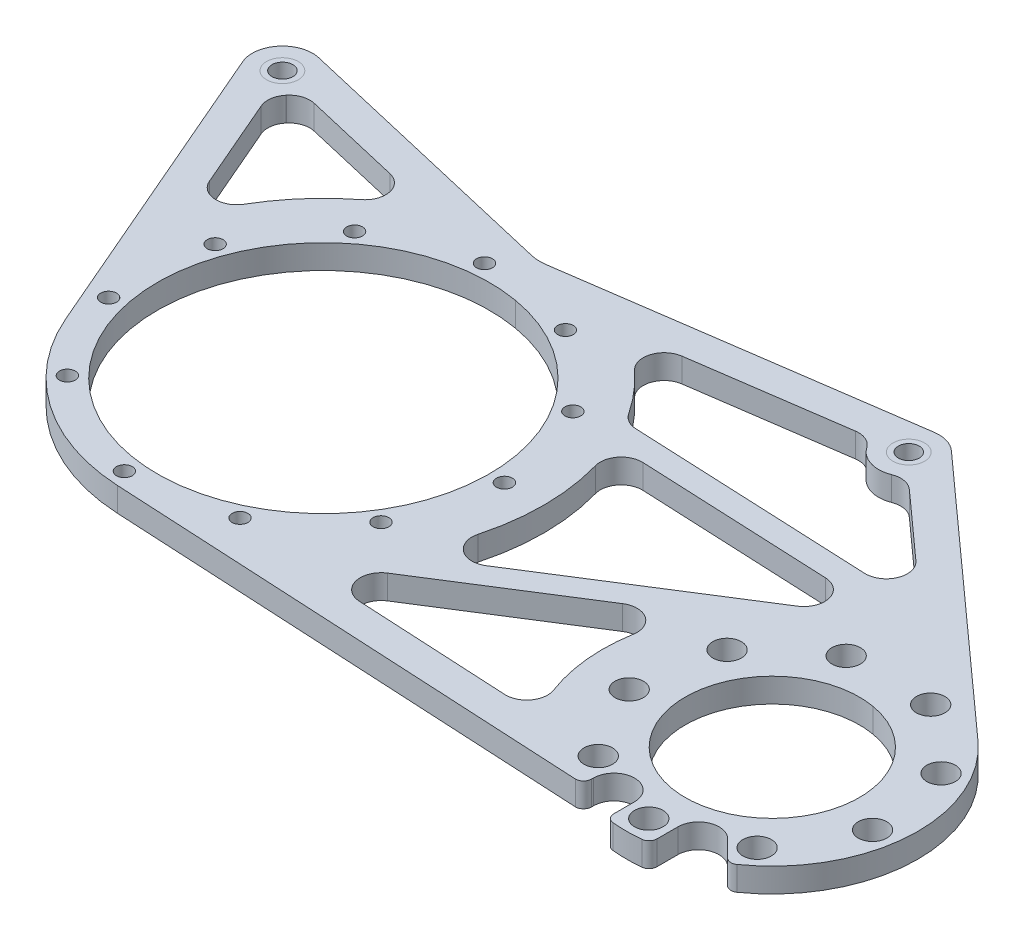
SolidWorks part; units mm, degrees
material "6061-T6 (SS)"
ref_plane "X-Y Datum" through (0, 0, 0) normal (0, 0, 1) x (1, 0, 0)
ref_plane "X-Z Datum" through (0, 0, 0) normal (0, 1, 0) x (1, 0, 0)
ref_plane "Y-Z Datum" through (0, 0, 0) normal (1, 0, 0) x (0, 0, -1)
sketch "Sketch2" plane through (0, 31.3819, 0) normal (0, 1, 0) x (1, 0, 0)
  line L0 (-693.7583, -176.702) -> (-693.7583, -183.2747) construction
  line L1 (-680.0808, -183.2747) -> (-680.0808, -176.702) construction
  line L2 (-668.9846, -172.1058) -> (-663.7197, -177.3707) construction
  line L3 (-693.7583, -176.702) -> (-693.7583, -183.2747)
  line L4 (-680.0808, -183.2747) -> (-680.0808, -176.702)
  line L5 (-668.9846, -172.1058) -> (-663.7197, -177.3707)
  line L6 (-966.641, -0.354) -> (-738.041, -0.354)
  line L7 (-727.7656, -5.5904) -> (-649.7224, -113.0358)
  line L9 (-977.8288, -19.0644) -> (-913.2312, -139.3061)
  line L10 (-706.7583, -177.279) -> (-706.7583, -176.702) construction
  line L11 (-706.7583, -177.279) -> (-706.7583, -176.702)
  line L12 (-861.9259, -171.8334) -> (-709.2983, -179.819)
  line L13 (-858.691, -110.0055) -> (-686.9195, -140.054) construction
  line L14 (-972.26, -24.9963) -> (-955.4664, -39.59) construction
  line L15 (-941.4162, -26.937) -> (-954.1775, -8.712) construction
  line L16 (-751.1929, -14.159) -> (-755.4346, -35.9995) construction
  line L17 (-737.4517, -41.8408) -> (-728.049, -21.6768) construction
  line L18 (-972.26, -24.9963) -> (-955.4664, -39.59)
  line L19 (-941.4162, -26.937) -> (-954.1775, -8.712)
  line L20 (-751.1929, -14.159) -> (-755.4346, -35.9995)
  line L21 (-737.4517, -41.8408) -> (-728.049, -21.6768)
  line L22 (-949.2186, -22.8753) -> (-746.0843, -28.2904)
  line L23 (-739.7146, -30.7335) -> (-656.1751, -105.8723)
  line L24 (-957.9647, -36.1729) -> (-915.5404, -134.527)
  arc A0 (-710.607, -179.4559) -> (-706.7583, -177.279) centre (-709.2983, -177.279) ccw construction
  arc A1 (-693.7583, -176.702) -> (-706.7583, -176.702) centre (-700.2583, -176.702) ccw construction
  arc A2 (-693.7583, -183.2747) -> (-691.4697, -185.8023) centre (-691.2183, -183.2747) ccw construction
  arc A3 (-691.4697, -185.8023) -> (-682.3694, -185.8023) centre (-686.9195, -140.054) ccw construction
  arc A4 (-682.3694, -185.8023) -> (-680.0808, -183.2747) centre (-682.6208, -183.2747) ccw construction
  arc A5 (-668.9846, -172.1058) -> (-680.0808, -176.702) centre (-673.5808, -176.702) ccw construction
  arc A6 (-663.7197, -177.3707) -> (-660.4619, -177.6519) centre (-661.9236, -175.5746) ccw construction
  arc A7 (-660.4619, -177.6519) -> (-710.607, -179.4559) centre (-686.9195, -140.054) ccw construction
  circle A8 centre (-858.691, -110.0055) radius 52.3875 construction
  circle A9 centre (-858.691, -110.0055) radius 61.9125 construction
  circle A10 centre (-738.041, -13.054) radius 12.7 construction
  circle A11 centre (-966.641, -13.054) radius 12.7 construction
  arc A12 (-710.607, -179.4559) -> (-706.7583, -177.279) centre (-709.2983, -177.279) ccw
  arc A13 (-693.7583, -176.702) -> (-706.7583, -176.702) centre (-700.2583, -176.702) ccw
  arc A14 (-693.7583, -183.2747) -> (-691.4697, -185.8023) centre (-691.2183, -183.2747) ccw
  arc A15 (-691.4697, -185.8023) -> (-682.3694, -185.8023) centre (-686.9195, -140.054) ccw
  arc A16 (-682.3694, -185.8023) -> (-680.0808, -183.2747) centre (-682.6208, -183.2747) ccw
  arc A17 (-668.9846, -172.1058) -> (-680.0808, -176.702) centre (-673.5808, -176.702) ccw
  arc A18 (-663.7197, -177.3707) -> (-660.4619, -177.6519) centre (-661.9236, -175.5746) ccw
  arc A19 (-660.4619, -177.6519) -> (-710.607, -179.4559) centre (-686.9195, -140.054) ccw
  circle A20 centre (-858.691, -110.0055) radius 52.3875
  circle A21 centre (-858.691, -110.0055) radius 61.9125
  circle A22 centre (-738.041, -13.054) radius 12.7
  circle A23 centre (-966.641, -13.054) radius 12.7
  circle A31 centre (-864.6648, -166.8424) radius 2.5 construction
  circle A39 centre (-864.6648, -166.8424) radius 2.5
  circle A40 centre (-686.9195, -140.054) radius 27.4955 construction
  circle A41 centre (-686.9195, -140.054) radius 27.4955
  circle A42 centre (-711.9883, -169.9297) radius 4.5 construction
  circle A43 centre (-725.3271, -146.8263) radius 4.5 construction
  circle A44 centre (-720.6945, -120.554) radius 4.5 construction
  circle A45 centre (-700.2583, -103.406) radius 4.5 construction
  circle A46 centre (-673.5808, -103.406) radius 4.5 construction
  circle A47 centre (-653.1446, -120.554) radius 4.5 construction
  circle A48 centre (-648.512, -146.8263) radius 4.5 construction
  circle A49 centre (-661.8508, -169.9297) radius 4.5 construction
  circle A50 centre (-686.9195, -179.054) radius 4.5 construction
  circle A51 centre (-711.9883, -169.9297) radius 4.5
  circle A52 centre (-725.3271, -146.8263) radius 4.5
  circle A53 centre (-720.6945, -120.554) radius 4.5
  circle A54 centre (-700.2583, -103.406) radius 4.5
  circle A55 centre (-673.5808, -103.406) radius 4.5
  circle A56 centre (-653.1446, -120.554) radius 4.5
  circle A57 centre (-648.512, -146.8263) radius 4.5
  circle A58 centre (-661.8508, -169.9297) radius 4.5
  circle A59 centre (-686.9195, -179.054) radius 4.5
  circle A60 centre (-966.641, -13.054) radius 3.3
  circle A61 centre (-738.041, -13.054) radius 3.3
  arc A62 (-955.4664, -39.59) -> (-941.4162, -26.937) centre (-949.2186, -32.4003) ccw construction
  arc A63 (-749.3237, -37.1863) -> (-742.8448, -38.4445) centre (-746.0843, -37.8154) ccw construction
  arc A64 (-742.8448, -38.4445) -> (-749.3237, -37.1863) centre (-746.0843, -37.8154) ccw construction
  arc A65 (-755.4346, -35.9995) -> (-737.4517, -41.8408) centre (-746.0843, -37.8154) ccw construction
  arc A66 (-955.4664, -39.59) -> (-941.4162, -26.937) centre (-949.2186, -32.4003) ccw
  arc A67 (-749.3237, -37.1863) -> (-742.8448, -38.4445) centre (-746.0843, -37.8154) ccw
  arc A68 (-742.8448, -38.4445) -> (-749.3237, -37.1863) centre (-746.0843, -37.8154) ccw
  arc A69 (-755.4346, -35.9995) -> (-737.4517, -41.8408) centre (-746.0843, -37.8154) ccw
  circle A70 centre (-949.2186, -32.4003) radius 3.3
  circle A71 centre (-949.2186, -32.4003) radius 9.525
  circle A72 centre (-746.0843, -37.8154) radius 9.525
  point P94 (-949.2186, -32.4003)
  dimension "D1" = 6.6
  dimension "D2" = 6.6
  dimension "D3" = 6.6
extrude "Boss-Extrude1" add sketch "Sketch2" along normal blind 7.62 contours A21 A39 A20 | A18 A19 A12 L11 A13 L3 A14 A15 A16 L4 A17 L5 A59 A58 A57 A56 A55 A54 A53 A52 A51 A41 | L13 A21 L12 A12 A19 | A21 L13 A19 L23 L21 A69 L20 L22 L19 A66 L18 L24 | A69 A72 A68 A67 | A72 L22 L20 | A72 L21 L23 | A71 L24 L18 | A71 L19 L22 | A71 A66 L22 A70 region at (-700.2583, 31.3819, 168.9016) region at (-773.051, 31.3819, 154.3682) region at (-890.9045, 31.3819, 160.8157) region at (-806.8861, 31.3819, 67.2042) region at (-956.9478, 31.3819, 38.0512) region at (-736.2382, 31.3819, 35.8095) region at (-956.6903, 31.3819, 37.8629) region at (-748.9437, 31.3819, 46.6182) region at (-752.4763, 31.3819, 29.8585) region at (-944.5842, 31.3819, 23.8004)
sketch "Sketch3" plane through (0, 31.3819, 0) normal (0, -1, 0) x (1, 0, 0)
  line L1 (-949.2186, 22.8753) -> (-746.0843, 28.2904) construction
  line L5 (-861.9259, 171.8334) -> (-709.2983, 179.819) construction
  line L6 (-977.8288, 19.0644) -> (-913.2312, 139.3061) construction
  line L7 (-727.7656, 5.5904) -> (-649.7224, 113.0358) construction
  line L13 (-751.1929, 14.159) -> (-755.4346, 35.9995) construction
  line L16 (-966.641, 0.354) -> (-738.041, 0.354) construction
  line L19 (-663.7197, 177.3707) -> (-668.9846, 172.1058)
  line L20 (-680.0808, 176.702) -> (-680.0808, 183.2747)
  line L21 (-693.7583, 183.2747) -> (-693.7583, 176.702)
  line L22 (-706.7583, 176.702) -> (-706.7583, 177.279)
  line L23 (-663.7197, 177.3707) -> (-668.9846, 172.1058)
  line L24 (-680.0808, 176.702) -> (-680.0808, 183.2747)
  line L25 (-693.7583, 183.2747) -> (-693.7583, 176.702)
  line L26 (-706.7583, 176.702) -> (-706.7583, 177.279)
  line L28 (-861.9259, 171.8334) -> (-709.2983, 179.819)
  line L29 (-977.8288, 19.0644) -> (-913.2312, 139.3061)
  line L30 (-727.7656, 5.5904) -> (-649.7224, 113.0358)
  line L31 (-966.641, 0.354) -> (-738.041, 0.354)
  line L34 (-737.4517, 41.8408) -> (-728.049, 21.6768) construction
  line L35 (-972.26, 24.9963) -> (-955.4664, 39.59) construction
  line L36 (-947.0539, 23.1246) -> (-856.9722, 44.1471)
  line L37 (-856.9722, 44.1471) -> (-747.4408, 28.3875)
  line L44 (-941.4162, 26.937) -> (-954.1775, 8.712) construction
  line L45 (-957.9647, 36.1729) -> (-915.5404, 134.527) construction
  line L46 (-739.7146, 30.7335) -> (-656.1751, 105.8723) construction
  line L47 (-861.9259, 171.8334) -> (-709.2983, 179.819)
  line L48 (-977.8288, 19.0644) -> (-913.2312, 139.3061)
  line L49 (-727.7656, 5.5904) -> (-649.7224, 113.0358)
  line L50 (-966.641, 0.354) -> (-738.041, 0.354)
  line L51 (-949.2186, 22.8753) -> (-746.0843, 28.2904)
  line L52 (-751.1929, 14.159) -> (-755.4346, 35.9995)
  line L53 (-737.4517, 41.8408) -> (-728.049, 21.6768)
  line L54 (-972.26, 24.9963) -> (-955.4664, 39.59)
  line L55 (-941.4162, 26.937) -> (-954.1775, 8.712)
  line L56 (-957.9647, 36.1729) -> (-915.5404, 134.527)
  line L57 (-739.7146, 30.7335) -> (-656.1751, 105.8723)
  arc A1 (-737.4517, 41.8408) -> (-755.4346, 35.9995) centre (-746.0843, 37.8154) ccw construction
  circle A3 centre (-966.641, 13.054) radius 12.7
  circle A5 centre (-966.641, 13.054) radius 12.7
  circle A7 centre (-738.041, 13.054) radius 12.7
  circle A9 centre (-738.041, 13.054) radius 12.7
  circle A11 centre (-858.691, 110.0055) radius 61.9125
  circle A13 centre (-858.691, 110.0055) radius 61.9125
  circle A15 centre (-858.691, 110.0055) radius 52.3875
  circle A17 centre (-858.691, 110.0055) radius 52.3875
  circle A19 centre (-686.9195, 140.054) radius 27.4955
  circle A21 centre (-686.9195, 140.054) radius 27.4955
  circle A23 centre (-864.6648, 166.8424) radius 2.5
  circle A25 centre (-864.6648, 166.8424) radius 2.5
  circle A51 centre (-720.6945, 120.554) radius 4.5
  circle A52 centre (-720.6945, 120.554) radius 4.5
  circle A68 centre (-725.3271, 146.8263) radius 4.5
  circle A69 centre (-725.3271, 146.8263) radius 4.5
  circle A70 centre (-711.9883, 169.9297) radius 4.5
  circle A71 centre (-711.9883, 169.9297) radius 4.5
  circle A72 centre (-738.041, 13.054) radius 3.3
  circle A73 centre (-738.041, 13.054) radius 3.3
  circle A74 centre (-966.641, 13.054) radius 3.3
  circle A75 centre (-966.641, 13.054) radius 3.3
  circle A76 centre (-686.9195, 179.054) radius 4.5
  circle A77 centre (-686.9195, 179.054) radius 4.5
  circle A78 centre (-661.8508, 169.9297) radius 4.5
  circle A79 centre (-661.8508, 169.9297) radius 4.5
  circle A80 centre (-648.512, 146.8263) radius 4.5
  circle A81 centre (-648.512, 146.8263) radius 4.5
  circle A82 centre (-653.1446, 120.554) radius 4.5
  circle A83 centre (-653.1446, 120.554) radius 4.5
  circle A84 centre (-673.5808, 103.406) radius 4.5
  circle A85 centre (-673.5808, 103.406) radius 4.5
  circle A86 centre (-700.2583, 103.406) radius 4.5
  circle A87 centre (-700.2583, 103.406) radius 4.5
  arc A95 (-710.607, 179.4559) -> (-660.4619, 177.6519) centre (-686.9195, 140.054) ccw
  arc A96 (-660.4619, 177.6519) -> (-663.7197, 177.3707) centre (-661.9236, 175.5746) ccw
  arc A97 (-680.0808, 176.702) -> (-668.9846, 172.1058) centre (-673.5808, 176.702) ccw
  arc A98 (-680.0808, 183.2747) -> (-682.3694, 185.8023) centre (-682.6208, 183.2747) ccw
  arc A99 (-682.3694, 185.8023) -> (-691.4697, 185.8023) centre (-686.9195, 140.054) ccw
  arc A100 (-691.4697, 185.8023) -> (-693.7583, 183.2747) centre (-691.2183, 183.2747) ccw
  arc A101 (-706.7583, 176.702) -> (-693.7583, 176.702) centre (-700.2583, 176.702) ccw
  arc A102 (-706.7583, 177.279) -> (-710.607, 179.4559) centre (-709.2983, 177.279) ccw
  arc A103 (-710.607, 179.4559) -> (-660.4619, 177.6519) centre (-686.9195, 140.054) ccw
  arc A104 (-660.4619, 177.6519) -> (-663.7197, 177.3707) centre (-661.9236, 175.5746) ccw
  arc A105 (-680.0808, 176.702) -> (-668.9846, 172.1058) centre (-673.5808, 176.702) ccw
  arc A106 (-680.0808, 183.2747) -> (-682.3694, 185.8023) centre (-682.6208, 183.2747) ccw
  arc A107 (-682.3694, 185.8023) -> (-691.4697, 185.8023) centre (-686.9195, 140.054) ccw
  arc A108 (-691.4697, 185.8023) -> (-693.7583, 183.2747) centre (-691.2183, 183.2747) ccw
  arc A109 (-706.7583, 176.702) -> (-693.7583, 176.702) centre (-700.2583, 176.702) ccw
  arc A110 (-706.7583, 177.279) -> (-710.607, 179.4559) centre (-709.2983, 177.279) ccw
  circle A152 centre (-746.0843, 37.8154) radius 9.525
  circle A153 centre (-746.0843, 37.8154) radius 9.525
  circle A154 centre (-949.2186, 32.4003) radius 9.525
  circle A155 centre (-949.2186, 32.4003) radius 9.525
  circle A156 centre (-949.2186, 32.4003) radius 3.3
  circle A157 centre (-949.2186, 32.4003) radius 3.3
  arc A158 (-941.4162, 26.937) -> (-955.4664, 39.59) centre (-949.2186, 32.4003) ccw construction
  arc A159 (-742.8448, 38.4445) -> (-749.3237, 37.1863) centre (-746.0843, 37.8154) ccw
  arc A160 (-749.3237, 37.1863) -> (-742.8448, 38.4445) centre (-746.0843, 37.8154) ccw
  arc A161 (-742.8448, 38.4445) -> (-749.3237, 37.1863) centre (-746.0843, 37.8154) ccw
  arc A162 (-749.3237, 37.1863) -> (-742.8448, 38.4445) centre (-746.0843, 37.8154) ccw
  arc A163 (-737.4517, 41.8408) -> (-755.4346, 35.9995) centre (-746.0843, 37.8154) ccw
  arc A164 (-941.4162, 26.937) -> (-955.4664, 39.59) centre (-949.2186, 32.4003) ccw
  dimension "D24" = 0
  dimension "D25" = 0
  dimension "D26" = 90.0818
  dimension "D27" = 21.0225
  dimension "D1" = 0
  dimension "D2" = 0
  dimension "D3" = 0
  dimension "D4" = 0
  dimension "D5" = 0
  dimension "D6" = 0
  dimension "D14" = 0
  dimension "D15" = 0
  dimension "D16" = 0
  dimension "D17" = 0
  dimension "D18" = 0
  dimension "D19" = 0
  dimension "D20" = 0
  dimension "D21" = 0
  dimension "D22" = 0
  dimension "D23" = 0
  dimension "D52" = 0
  dimension "D53" = 0
  dimension "D54" = 0
  dimension "D55" = 0
ref_point "Point1"
ref_point "Point2"
ref_plane "Plane1" through (-858.691, 31.3819, 110.0055) normal (0.985, 0, 0.1723) x (0.1723, 0, -0.985)
ref_plane "Plane2" through (-686.9195, 31.3819, 140.054) normal (-0.985, 0, -0.1723) x (-0.1723, 0, 0.985)
split line "Split Line1"
split line "Split Line2"
ref_axis "Axis1" through (-858.691, 39.0019, 110.0055) along (0, -1, 0)
ref_axis "Axis2" through (-686.9195, 39.0019, 140.054) along (0, -1, 0)
extrude "Cut-Extrude1" cut sketch "Sketch3" against normal through all contours L36 L55 L51 L52 L37 | A155 L51 L55 L36 | A153 L37 L52 L51 region at (-751.5495, 31.3819, 28.5688) region at (-850.6911, 31.3819, 31.7926) region at (-945.2616, 31.3819, 23.2848)
fillet "Fillet2" radius 12.7 1 edges at (-856.9722, 35.1919, 44.1471)
sketch "Sketch4" plane through (0, 31.3819, 0) normal (0, -1, 0) x (1, 0, 0)
  line L0 (-861.9259, 171.8334) -> (-709.2983, 179.819) construction
  line L1 (-727.7656, 5.5904) -> (-649.7224, 113.0358) construction
  line L2 (-977.8288, 19.0644) -> (-913.2312, 139.3061) construction
  line L4 (-706.7583, 176.702) -> (-706.7583, 177.279)
  line L5 (-663.7197, 177.3707) -> (-668.9846, 172.1058)
  line L6 (-680.0808, 176.702) -> (-680.0808, 183.2747)
  line L7 (-693.7583, 183.2747) -> (-693.7583, 176.702)
  line L8 (-706.7583, 176.702) -> (-706.7583, 177.279)
  line L9 (-663.7197, 177.3707) -> (-668.9846, 172.1058)
  line L10 (-680.0808, 176.702) -> (-680.0808, 183.2747)
  line L11 (-693.7583, 183.2747) -> (-693.7583, 176.702)
  line L13 (-966.641, 0.354) -> (-738.041, 0.354) construction
  line L14 (-861.9259, 171.8334) -> (-709.2983, 179.819)
  line L15 (-727.7656, 5.5904) -> (-649.7224, 113.0358)
  line L16 (-977.8288, 19.0644) -> (-913.2312, 139.3061)
  line L17 (-861.9259, 171.8334) -> (-709.2983, 179.819) construction
  line L19 (-966.641, 0.354) -> (-738.041, 0.354)
  line L20 (-924.6037, 87.863) -> (-948.1369, 33.3048)
  line L21 (-948.1369, 33.3048) -> (-888.5504, 47.2106)
  line L22 (-732.3805, 168.4374) -> (-812.7818, 164.2308)
  line L23 (-812.7818, 164.2308) -> (-733.9678, 114.3873)
  line L24 (-799.833, 147.0258) -> (-703.8013, 86.2934)
  line L25 (-703.8013, 86.2934) -> (-794.9695, 82.1785)
  line L26 (-824.108, 49.6832) -> (-755.4008, 39.7974)
  line L27 (-798.9847, 74.3695) -> (-701.5009, 78.7695)
  line L28 (-701.5009, 78.7695) -> (-739.4428, 44.643)
  line L29 (-977.8288, 19.0644) -> (-913.2312, 139.3061) construction
  line L30 (-727.7656, 5.5904) -> (-649.7224, 113.0358) construction
  line L31 (-966.641, 0.354) -> (-738.041, 0.354) construction
  line L32 (-663.7197, 177.3707) -> (-668.9846, 172.1058)
  line L33 (-680.0808, 176.702) -> (-680.0808, 183.2747)
  line L34 (-693.7583, 183.2747) -> (-693.7583, 176.702)
  line L35 (-706.7583, 176.702) -> (-706.7583, 177.279)
  line L36 (-663.7197, 177.3707) -> (-668.9846, 172.1058)
  line L37 (-680.0808, 176.702) -> (-680.0808, 183.2747)
  line L38 (-693.7583, 183.2747) -> (-693.7583, 176.702)
  line L39 (-706.7583, 176.702) -> (-706.7583, 177.279)
  line L40 (-949.2186, 22.8753) -> (-746.0843, 28.2904) construction
  line L41 (-751.1929, 14.159) -> (-755.4346, 35.9995) construction
  line L42 (-737.4517, 41.8408) -> (-728.049, 21.6768) construction
  line L43 (-972.26, 24.9963) -> (-955.4664, 39.59) construction
  line L44 (-941.4162, 26.937) -> (-954.1775, 8.712) construction
  line L45 (-957.9647, 36.1729) -> (-915.5404, 134.527) construction
  line L46 (-739.7146, 30.7335) -> (-656.1751, 105.8723) construction
  line L47 (-861.9259, 171.8334) -> (-709.2983, 179.819)
  line L48 (-977.8288, 19.0644) -> (-913.2312, 139.3061)
  line L49 (-727.7656, 5.5904) -> (-649.7224, 113.0358)
  line L50 (-966.641, 0.354) -> (-738.041, 0.354)
  line L51 (-949.2186, 22.8753) -> (-746.0843, 28.2904)
  line L52 (-751.1929, 14.159) -> (-755.4346, 35.9995)
  line L53 (-737.4517, 41.8408) -> (-728.049, 21.6768)
  line L54 (-972.26, 24.9963) -> (-955.4664, 39.59)
  line L55 (-941.4162, 26.937) -> (-954.1775, 8.712)
  line L56 (-957.9647, 36.1729) -> (-915.5404, 134.527)
  line L57 (-739.7146, 30.7335) -> (-656.1751, 105.8723)
  line L58 (-947.0539, 23.1246) -> (-859.3005, 43.6037) construction
  line L60 (-854.6056, 43.8066) -> (-747.4408, 28.3875) construction
  circle A1 centre (-858.691, 110.0055) radius 52.3875
  circle A2 centre (-858.691, 110.0055) radius 52.3875
  circle A3 centre (-858.691, 110.0055) radius 61.9125
  circle A4 centre (-858.691, 110.0055) radius 61.9125
  circle A5 centre (-738.041, 13.054) radius 12.7
  circle A6 centre (-738.041, 13.054) radius 12.7
  circle A7 centre (-966.641, 13.054) radius 12.7
  circle A8 centre (-966.641, 13.054) radius 12.7
  circle A17 centre (-864.6648, 166.8424) radius 2.5
  circle A18 centre (-864.6648, 166.8424) radius 2.5
  circle A19 centre (-686.9195, 140.054) radius 27.4955
  circle A20 centre (-686.9195, 140.054) radius 27.4955
  circle A21 centre (-725.3271, 146.8263) radius 4.5
  circle A22 centre (-725.3271, 146.8263) radius 4.5
  circle A23 centre (-720.6945, 120.554) radius 4.5
  circle A24 centre (-720.6945, 120.554) radius 4.5
  circle A31 centre (-661.8508, 169.9297) radius 4.5
  circle A32 centre (-661.8508, 169.9297) radius 4.5
  circle A33 centre (-686.9195, 179.054) radius 4.5
  circle A34 centre (-686.9195, 179.054) radius 4.5
  circle A35 centre (-966.641, 13.054) radius 3.3
  circle A36 centre (-966.641, 13.054) radius 3.3
  circle A37 centre (-738.041, 13.054) radius 3.3
  circle A38 centre (-738.041, 13.054) radius 3.3
  circle A39 centre (-711.9883, 169.9297) radius 4.5
  circle A40 centre (-711.9883, 169.9297) radius 4.5
  circle A41 centre (-700.2583, 103.406) radius 4.5
  circle A42 centre (-700.2583, 103.406) radius 4.5
  circle A43 centre (-673.5808, 103.406) radius 4.5
  circle A44 centre (-673.5808, 103.406) radius 4.5
  circle A45 centre (-653.1446, 120.554) radius 4.5
  circle A46 centre (-653.1446, 120.554) radius 4.5
  circle A47 centre (-648.512, 146.8263) radius 4.5
  circle A48 centre (-648.512, 146.8263) radius 4.5
  arc A49 (-888.5504, 47.2106) -> (-924.6037, 87.863) centre (-858.691, 110.0055) cw
  arc A50 (-732.3805, 168.4374) -> (-733.9678, 114.3873) centre (-686.9195, 140.054) ccw
  arc A51 (-799.833, 147.0258) -> (-794.9695, 82.1785) centre (-858.691, 110.0055) cw
  arc A52 (-824.108, 49.6832) -> (-798.9847, 74.3695) centre (-858.691, 110.0055) ccw
  arc A53 (-737.4517, 41.8408) -> (-755.4346, 35.9995) centre (-746.0843, 37.8154) ccw construction
  circle A54 centre (-966.641, 13.054) radius 12.7
  circle A55 centre (-966.641, 13.054) radius 12.7
  arc A56 (-706.7583, 177.279) -> (-710.607, 179.4559) centre (-709.2983, 177.279) ccw
  arc A57 (-710.607, 179.4559) -> (-660.4619, 177.6519) centre (-686.9195, 140.054) ccw
  arc A58 (-660.4619, 177.6519) -> (-663.7197, 177.3707) centre (-661.9236, 175.5746) ccw
  arc A59 (-680.0808, 176.702) -> (-668.9846, 172.1058) centre (-673.5808, 176.702) ccw
  arc A60 (-680.0808, 183.2747) -> (-682.3694, 185.8023) centre (-682.6208, 183.2747) ccw
  arc A61 (-682.3694, 185.8023) -> (-691.4697, 185.8023) centre (-686.9195, 140.054) ccw
  arc A62 (-691.4697, 185.8023) -> (-693.7583, 183.2747) centre (-691.2183, 183.2747) ccw
  arc A63 (-706.7583, 176.702) -> (-693.7583, 176.702) centre (-700.2583, 176.702) ccw
  arc A64 (-706.7583, 177.279) -> (-710.607, 179.4559) centre (-709.2983, 177.279) ccw
  arc A65 (-710.607, 179.4559) -> (-660.4619, 177.6519) centre (-686.9195, 140.054) ccw
  arc A66 (-660.4619, 177.6519) -> (-663.7197, 177.3707) centre (-661.9236, 175.5746) ccw
  arc A67 (-680.0808, 176.702) -> (-668.9846, 172.1058) centre (-673.5808, 176.702) ccw
  arc A68 (-680.0808, 183.2747) -> (-682.3694, 185.8023) centre (-682.6208, 183.2747) ccw
  arc A69 (-682.3694, 185.8023) -> (-691.4697, 185.8023) centre (-686.9195, 140.054) ccw
  arc A70 (-691.4697, 185.8023) -> (-693.7583, 183.2747) centre (-691.2183, 183.2747) ccw
  arc A71 (-706.7583, 176.702) -> (-693.7583, 176.702) centre (-700.2583, 176.702) ccw
  circle A72 centre (-738.041, 13.054) radius 12.7
  circle A73 centre (-738.041, 13.054) radius 12.7
  circle A74 centre (-858.691, 110.0055) radius 61.9125
  circle A75 centre (-858.691, 110.0055) radius 61.9125
  circle A76 centre (-858.691, 110.0055) radius 52.3875
  circle A77 centre (-858.691, 110.0055) radius 52.3875
  circle A78 centre (-686.9195, 140.054) radius 27.4955
  circle A79 centre (-686.9195, 140.054) radius 27.4955
  circle A80 centre (-864.6648, 166.8424) radius 2.5
  circle A81 centre (-864.6648, 166.8424) radius 2.5
  circle A96 centre (-720.6945, 120.554) radius 4.5
  circle A97 centre (-720.6945, 120.554) radius 4.5
  circle A98 centre (-725.3271, 146.8263) radius 4.5
  circle A99 centre (-725.3271, 146.8263) radius 4.5
  circle A100 centre (-711.9883, 169.9297) radius 4.5
  circle A101 centre (-711.9883, 169.9297) radius 4.5
  circle A102 centre (-738.041, 13.054) radius 3.3
  circle A103 centre (-738.041, 13.054) radius 3.3
  circle A104 centre (-966.641, 13.054) radius 3.3
  circle A105 centre (-966.641, 13.054) radius 3.3
  circle A106 centre (-686.9195, 179.054) radius 4.5
  circle A107 centre (-686.9195, 179.054) radius 4.5
  circle A108 centre (-661.8508, 169.9297) radius 4.5
  circle A109 centre (-661.8508, 169.9297) radius 4.5
  circle A110 centre (-648.512, 146.8263) radius 4.5
  circle A111 centre (-648.512, 146.8263) radius 4.5
  circle A112 centre (-653.1446, 120.554) radius 4.5
  circle A113 centre (-653.1446, 120.554) radius 4.5
  circle A114 centre (-673.5808, 103.406) radius 4.5
  circle A115 centre (-673.5808, 103.406) radius 4.5
  circle A116 centre (-700.2583, 103.406) radius 4.5
  circle A117 centre (-700.2583, 103.406) radius 4.5
  circle A118 centre (-746.0843, 37.8154) radius 9.525
  circle A119 centre (-746.0843, 37.8154) radius 9.525
  circle A120 centre (-949.2186, 32.4003) radius 9.525
  circle A121 centre (-949.2186, 32.4003) radius 9.525
  circle A122 centre (-949.2186, 32.4003) radius 3.3
  circle A123 centre (-949.2186, 32.4003) radius 3.3
  arc A124 (-941.4162, 26.937) -> (-955.4664, 39.59) centre (-949.2186, 32.4003) ccw construction
  arc A125 (-742.8448, 38.4445) -> (-749.3237, 37.1863) centre (-746.0843, 37.8154) ccw
  arc A126 (-749.3237, 37.1863) -> (-742.8448, 38.4445) centre (-746.0843, 37.8154) ccw
  arc A127 (-742.8448, 38.4445) -> (-749.3237, 37.1863) centre (-746.0843, 37.8154) ccw
  arc A128 (-749.3237, 37.1863) -> (-742.8448, 38.4445) centre (-746.0843, 37.8154) ccw
  arc A129 (-737.4517, 41.8408) -> (-755.4346, 35.9995) centre (-746.0843, 37.8154) ccw
  arc A130 (-941.4162, 26.937) -> (-955.4664, 39.59) centre (-949.2186, 32.4003) ccw
  arc A135 (-710.607, 179.4559) -> (-660.4619, 177.6519) centre (-686.9195, 140.054) ccw
  arc A136 (-660.4619, 177.6519) -> (-663.7197, 177.3707) centre (-661.9236, 175.5746) ccw
  arc A137 (-680.0808, 176.702) -> (-668.9846, 172.1058) centre (-673.5808, 176.702) ccw
  arc A138 (-680.0808, 183.2747) -> (-682.3694, 185.8023) centre (-682.6208, 183.2747) ccw
  arc A139 (-682.3694, 185.8023) -> (-691.4697, 185.8023) centre (-686.9195, 140.054) ccw
  arc A140 (-691.4697, 185.8023) -> (-693.7583, 183.2747) centre (-691.2183, 183.2747) ccw
  arc A141 (-706.7583, 176.702) -> (-693.7583, 176.702) centre (-700.2583, 176.702) ccw
  arc A142 (-706.7583, 177.279) -> (-710.607, 179.4559) centre (-709.2983, 177.279) ccw
  arc A143 (-710.607, 179.4559) -> (-660.4619, 177.6519) centre (-686.9195, 140.054) ccw
  arc A144 (-660.4619, 177.6519) -> (-663.7197, 177.3707) centre (-661.9236, 175.5746) ccw
  arc A145 (-680.0808, 176.702) -> (-668.9846, 172.1058) centre (-673.5808, 176.702) ccw
  arc A146 (-680.0808, 183.2747) -> (-682.3694, 185.8023) centre (-682.6208, 183.2747) ccw
  arc A147 (-682.3694, 185.8023) -> (-691.4697, 185.8023) centre (-686.9195, 140.054) ccw
  arc A148 (-691.4697, 185.8023) -> (-693.7583, 183.2747) centre (-691.2183, 183.2747) ccw
  arc A149 (-706.7583, 176.702) -> (-693.7583, 176.702) centre (-700.2583, 176.702) ccw
  arc A150 (-706.7583, 177.279) -> (-710.607, 179.4559) centre (-709.2983, 177.279) ccw
  dimension "D26" = 7.62
  dimension "D29" = 7.62
  dimension "D30" = 7.62
  dimension "D35" = 0
  dimension "D39" = 7.62
  dimension "D27" = 0
  dimension "D28" = 0
  dimension "D31" = 10.16
  dimension "D32" = 7.62
  dimension "D33" = 93.2524
  dimension "D34" = 49.8435
  dimension "D36" = 91.1683
  dimension "D37" = 4.1149
  dimension "D38" = 10.16
  dimension "D40" = 7.62
  dimension "D67" = 10.16
  dimension "D68" = 10.16
  dimension "D69" = 10.16
  dimension "D1" = 0
  dimension "D2" = 0
  dimension "D3" = 0
  dimension "D4" = 0
  dimension "D9" = 0
  dimension "D10" = 0
  dimension "D11" = 0
  dimension "D12" = 0
  dimension "D16" = 0
  dimension "D17" = 0
  dimension "D18" = 0
  dimension "D19" = 0
  dimension "D20" = 0
  dimension "D21" = 0
  dimension "D22" = 0
  dimension "D23" = 0
  dimension "D24" = 0
  dimension "D25" = 0
  dimension "D41" = 0
  dimension "D42" = 0
  dimension "D43" = 0
  dimension "D51" = 0
  dimension "D52" = 0
  dimension "D53" = 0
  dimension "D54" = 0
  dimension "D55" = 0
  dimension "D56" = 0
  dimension "D57" = 0
  dimension "D58" = 0
  dimension "D59" = 0
  dimension "D60" = 0
  dimension "D61" = 0
  dimension "D62" = 0
  dimension "D63" = 0
  dimension "D64" = 0
  dimension "D65" = 0
  dimension "D66" = 0
extrude "Cut-Extrude2" cut sketch "Sketch4" against normal through all contours L21 A49 L20 A8 | A52 L26 A6 L28 L27 | L24 A51 L25 | A50 L22 L23 region at (-763.7407, 31.3819, 60.8107) region at (-921.8341, 31.3819, 54.9859) region at (-763.0306, 31.3819, 150.0769) region at (-762.4094, 31.3819, 103.8535)
fillet "Fillet3" radius 6.604 15 edges at (-733.9678, 35.1919, 114.3873) (-732.3805, 35.1919, 168.4374) (-812.7818, 35.1919, 164.2308) (-703.8013, 35.1919, 86.2934) (-794.9695, 35.1919, 82.1785) (-799.833, 35.1919, 147.0258) (-701.5009, 35.1919, 78.7695) (-798.9847, 35.1919, 74.3695) (-824.108, 35.1919, 49.6832) (-888.5504, 35.1919, 47.2106) (-924.6037, 35.1919, 87.863) (-739.4428, 35.1919, 44.643) (-755.4008, 35.1919, 39.7974) (-940.1078, 35.1919, 35.1786) (-944.8714, 35.1919, 40.8754)
split line "Split Line3"
sketch "Sketch2<4>" plane through (0, 31.3819, 0) normal (0, 1, 0) x (1, 0, 0) same geometry as "Sketch2"
pattern_circular "CirPattern2" count 11 every 32 about axis through (-858.691, 39.0019, 110.0055) along (0, -1, 0) reverse direction yes of face at (-867.1648, 39.0019, 166.8424)
sketch "Sketch5" plane through (0, 39.0019, 0) normal (0, 1, 0) x (1, 0, 0)
  circle A0 centre (-949.2186, -32.4003) radius 5
  circle A1 centre (-746.0843, -37.8154) radius 5
  dimension "D1" = 10
split line "Split Line4"
sketch "Sketch6" [suppressed] plane through (0, 31.3819, 0) normal (0, -1, 0) x (1, 0, 0)
  line L0 (-743.6056, 167.8501) -> (-792.0577, 165.3151) construction
  line L1 (-724.7926, 85.346) -> (-785.1492, 82.6217) construction
  line L2 (-724.7926, 85.346) -> (-785.1492, 82.6217)
  line L3 (-791.5915, 128.2378) -> (-796.8267, 141.9391)
  line L4 (-743.6056, 167.8501) -> (-781.2512, 165.8805)
  line L5 (-781.2512, 165.8805) -> (-792.0577, 165.3151)
  arc A0 (-791.8001, 91.022) -> (-791.5915, 128.2378) centre (-858.691, 110.0055) ccw construction
  arc A1 (-791.8001, 91.022) -> (-791.5915, 128.2378) centre (-858.691, 110.0055) ccw
  circle A2 centre (-780.3284, 148.243) radius 17.6616 construction
  circle A3 centre (-744.0706, 102.1866) radius 14.9639 construction
  arc A4 (-737.0797, 158.9293) -> (-739.7578, 131.0856) centre (-686.9195, 140.054) ccw construction
  arc A5 (-724.7926, 85.346) -> (-721.5605, 97.5247) centre (-725.0904, 91.9433) ccw construction
  arc A6 (-737.0797, 158.9293) -> (-743.6056, 167.8501) centre (-743.2606, 161.2551) ccw construction
  arc A7 (-737.0797, 158.9293) -> (-739.7578, 131.0856) centre (-686.9195, 140.054) ccw
  arc A8 (-737.0797, 158.9293) -> (-743.6056, 167.8501) centre (-743.2606, 161.2551) ccw
  arc A9 (-724.7926, 85.346) -> (-721.5605, 97.5247) centre (-725.0904, 91.9433) ccw
  arc A10 (-791.8001, 91.022) -> (-785.1492, 82.6217) centre (-785.447, 89.219) ccw construction
  arc A11 (-791.8001, 91.022) -> (-785.1492, 82.6217) centre (-785.447, 89.219) ccw
  arc A13 (-739.7578, 131.0856) -> (-731.5964, 110.4517) centre (-686.9195, 140.054) ccw
  arc A14 (-721.5605, 97.5247) -> (-731.5964, 110.4517) centre (-640.5401, 170.7843) cw
  arc A15 (-792.0577, 165.3151) -> (-798.1017, 160.3912) centre (-791.7127, 158.7201) ccw
  arc A17 (-792.0577, 165.3151) -> (-795.2425, 153.1386) centre (-791.7127, 158.7201) ccw construction
  arc A18 (-798.1017, 160.3912) -> (-796.8267, 141.9391) centre (-767.2093, 153.2558) ccw
  dimension "D3" = 31.7058
  dimension "D1" = 11.2631
  dimension "D2" = 22.5101
